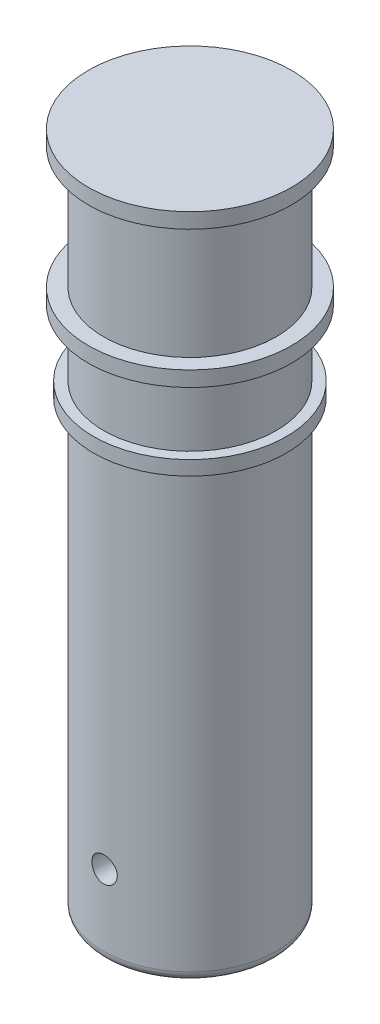
SolidWorks part; units mm, degrees
material "ABS"
ref_plane "Front Plane" through (0, 0, 0) normal (0, 0, 1) x (1, 0, 0)
ref_plane "Top Plane" through (0, 0, 0) normal (0, 1, 0) x (1, 0, 0)
ref_plane "Right Plane" through (0, 0, 0) normal (1, 0, 0) x (0, 0, -1)
sketch "Sketch1" plane through (0, 0, 0) normal (0, 0, 1) x (1, 0, 0)
  line L2 (-8.5, -51.915) -> (-8.5, -7.915)
  line L3 (-8.5, 0) -> (-10, 0)
  line L4 (-10, 0) -> (-10, 1.5)
  line L5 (-10, 1.5) -> (-8.5, 1.5)
  line L6 (-8.5, 1.5) -> (-8.5, 13.5)
  line L7 (-8.5, 13.5) -> (-10, 13.5)
  line L8 (-10, 13.5) -> (-10, 15)
  line L9 (-10, 15) -> (0, 15)
  line L10 (0, 15) -> (0, -37.915)
  line L11 (-4, -51.915) -> (-8.5, -51.915)
  line L12 (-4, -37.915) -> (-4, -51.915)
  line L13 (0, -37.915) -> (-4, -37.915)
  line L14 (-8.5, -7.915) -> (-9.5, -7.915)
  line L16 (-9.5, -7.915) -> (-9.5, -6.5)
  line L17 (-9.5, -6.5) -> (-8.5, -6.5)
  line L18 (-8.5, -6.5) -> (-8.5, 0)
  dimension "D1" = 8.5
  dimension "D2" = 1.5
  dimension "D3" = 51.915
  dimension "D4" = 1.5
  dimension "D5" = 4
  dimension "D6" = 14
  dimension "D7" = 15
  dimension "D8" = 10
  dimension "D9" = 44
  dimension "D10" = 1
  dimension "6.5" = 6.5
revolve "Revolve1" add sketch "Sketch1" angle 360 about L10
fillet "Fillet1" radius 1 2 edges at (-8.5, -51.915, 0) (-4, -51.915, 0)
hole_wizard "M3x0.5 Tapped Hole1" positions "Sketch2" profile "Sketch3" tap size "M3x0.5" standard "ANSI Metric" end condition up to next
sketch "Sketch2" plane through (0, 0, 0) normal (0, 0, 1) x (1, 0, 0)
  line L0 (-7.5, -51.915) -> (7.5, -51.915) construction
  point P0 (0, -43.915)
  dimension "D1" = 8
sketch "Sketch3" plane through (0, -43.915, 0) normal (1, 0, 0) x (0, 1, 0)
  line L0 (0, 0) -> (0, 8.5)
  line L1 (0, 8.5) -> (1.25, 8.5)
  line L2 (1.25, 8.5) -> (1.25, 0)
  line L5 (1.25, 0) -> (0, 0)
  line L11 (0, -6.35) -> (0, 107.95) construction
  dimension "Thru Tap Drill Dia." = 2.5
  dimension "Thru Tap Drill Depth" = 8.5
cosmetic thread "Hole Thread1" parameters "D2"=3
